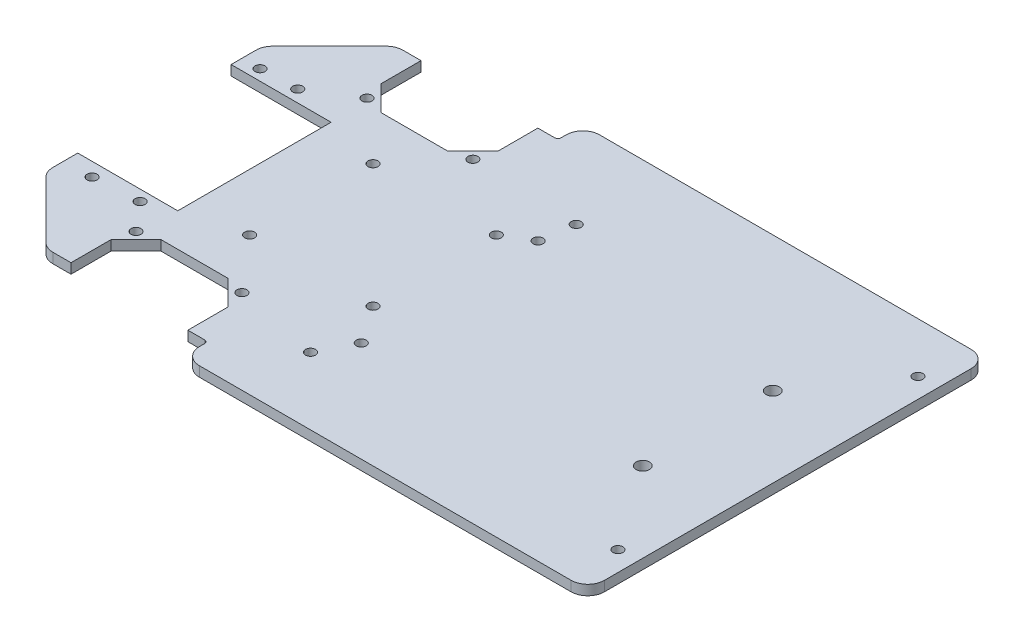
SolidWorks part; units mm, degrees
ref_plane "Front Plane" through (0, 0, 0) normal (0, 0, 1) x (1, 0, 0)
ref_plane "Top Plane" through (0, 0, 0) normal (0, 1, 0) x (1, 0, 0)
ref_plane "Right Plane" through (0, 0, 0) normal (1, 0, 0) x (0, 0, -1)
sketch "Sketch1" plane through (0, 0, 0) normal (0, 1, 0) x (1, 0, 0)
  line L0 (190, 0) -> (0, 0) construction
  line L1 (0, -60) -> (190, -60)
  line L2 (0, -60) -> (0, 60)
  line L3 (0, 60) -> (190, 60)
  line L4 (190, -60) -> (190, 60)
  line L5 (0, -32.5266) -> (27.4734, -60)
  line L6 (30, 23) -> (0, 23) construction
  line L7 (30, 23) -> (30, -23) construction
  line L8 (30, -23) -> (0, -23) construction
  line L9 (0, 23) -> (0, -23)
  line L10 (30, 23) -> (0, -23) construction
  line L11 (30, -23) -> (0, 23) construction
  line L12 (19.9734, -52.5) -> (27.4734, -52.5) construction
  line L13 (68.5266, -52.5) -> (68.5266, -60) construction
  line L14 (35, -33) -> (27.4734, -40.5266) construction
  line L15 (27.4734, -52.5) -> (27.4734, -40.5266) construction
  line L16 (27.4734, -40.5266) -> (27.4734, -52.5) construction
  line L17 (0, 32.5266) -> (27.4734, 60)
  line L18 (35, -33) -> (55, -33) construction
  line L19 (55, -33) -> (62.5266, -40.5266) construction
  line L20 (62.5266, -52.5) -> (68.5266, -52.5) construction
  line L21 (47.5, -37) -> (42.5, -37) construction
  line L22 (45, -37) -> (45, -33) construction
  line L23 (45, -56.5) -> (45, -52.5) construction
  line L24 (39.4, -56.5) -> (50.6, -56.5) construction
  line L25 (27.4734, -52.5) -> (62.5266, -52.5) construction
  line L27 (62.5266, -40.5266) -> (62.5266, -52.5) construction
  point P7 (0, 0)
  point P8 (15, 0)
  dimension "D1" = 120
  dimension "D2" = 190
  dimension "D3" = 30
  dimension "D4" = 23
  dimension "D5" = 10
  dimension "D6" = 20
  dimension "D7" = 45
  dimension "D8" = 45
  dimension "D9" = 45
  dimension "D10" = 7.5
  dimension "D11" = 6
extrude "Boss-Extrude1" add sketch "Sketch1" along normal blind 3 contours L7 L8 L2 L1 L4 L3 L6 region at (97.9391, 0, 0)
sketch "Sketch4" plane through (0, 0, 0) normal (0, 1, 0) x (1, 0, 0)
  line L0 (68.5266, -60) -> (68.5266, -52.5)
  line L1 (68.5266, -52.5) -> (62.5266, -52.5)
  line L2 (62.5266, -52.5) -> (62.5266, -40.5266)
  line L3 (62.5266, -40.5266) -> (55, -33)
  line L4 (55, -33) -> (35, -33)
  line L5 (35, -33) -> (27.4734, -40.5266)
  line L6 (27.4734, -40.5266) -> (27.4734, -52.5)
  line L7 (27.4734, -52.5) -> (19.9734, -52.5)
  line L8 (19.9734, -52.5) -> (27.4734, -60)
  line L9 (27.4734, -60) -> (68.5266, -60)
  line L10 (0, 0) -> (190, 0) construction
  line L11 (190, -60) -> (190, 60) construction
  line L12 (27.4734, 60) -> (68.5266, 60)
  line L13 (19.9734, 52.5) -> (27.4734, 60)
  line L14 (27.4734, 52.5) -> (19.9734, 52.5)
  line L15 (27.4734, 40.5266) -> (27.4734, 52.5)
  line L16 (35, 33) -> (27.4734, 40.5266)
  line L17 (55, 33) -> (35, 33)
  line L18 (62.5266, 40.5266) -> (55, 33)
  line L19 (62.5266, 52.5) -> (62.5266, 40.5266)
  line L20 (68.5266, 52.5) -> (62.5266, 52.5)
  line L21 (68.5266, 60) -> (68.5266, 52.5)
  line L23 (30, 23) -> (0, 23)
  line L24 (30, 23) -> (30, -23)
  line L25 (30, -23) -> (0, -23)
  line L26 (0, 23) -> (0, -23)
extrude "Cut-Extrude1" cut sketch "Sketch4" along normal up to surface (3 mm away) up to face at (72.4911, 3, 0)
fillet "Fillet1" radius 5 8 edges at (19.9734, 1.5, -52.5) (0, 1.5, -32.5266) (68.5266, 1.5, -60) (190, 1.5, -60) (190, 1.5, 60) (0, 1.5, 32.5266) (19.9734, 1.5, 52.5) (68.5266, 1.5, 60)
fillet "Fillet2" radius 1 2 edges at (68.5266, 1.5, -52.5) (68.5266, 1.5, 52.5)
sketch "Sketch5" plane through (0, 0, 0) normal (0, 1, 0) x (1, 0, 0)
  circle A0 centre (47.0626, -18.5) radius 1.5 construction
  circle A1 centre (47.0626, -18.5) radius 1.5
  circle A2 centre (84.0626, -18.5) radius 1.5 construction
  circle A3 centre (84.0626, -18.5) radius 1.5
  circle A4 centre (84.0626, 18.5) radius 1.5 construction
  circle A5 centre (84.0626, 18.5) radius 1.5
  circle A6 centre (47.0626, 18.5) radius 1.5 construction
  circle A7 centre (47.0626, 18.5) radius 1.5
  circle A8 centre (91.88, 23.2195) radius 1.5 construction
  circle A9 centre (91.88, 23.2195) radius 1.5
  circle A10 centre (93.3054, 33.2195) radius 1.5 construction
  circle A11 centre (93.3054, 33.2195) radius 1.5
  circle A12 centre (29.1154, 34.642) radius 1.5 construction
  circle A13 centre (60.8846, 34.642) radius 1.5 construction
  circle A14 centre (8.3674, -27.0854) radius 1.5 construction
  circle A15 centre (16.3794, 26.6064) radius 1.5 construction
  circle A16 centre (91.88, -29.8422) radius 1.5 construction
  circle A17 centre (86.6598, -39.8422) radius 1.5 construction
  circle A18 centre (29.1154, 34.642) radius 1.5
  circle A19 centre (60.8846, 34.642) radius 1.5
  circle A20 centre (8.3674, -27.0854) radius 1.5
  circle A21 centre (16.3794, 26.6064) radius 1.5
  circle A22 centre (91.88, -29.8422) radius 1.5
  circle A23 centre (86.6598, -39.8422) radius 1.5
  circle A24 centre (184.0458, -45) radius 1.5 construction
  circle A25 centre (184.0458, 45) radius 1.5 construction
  circle A26 centre (184.0458, -45) radius 1.5
  circle A27 centre (184.0458, 45) radius 1.5
  circle A28 centre (166, -19.5) radius 2 construction
  circle A29 centre (166, 19.5) radius 2 construction
  circle A30 centre (166, -19.5) radius 2
  circle A31 centre (166, 19.5) radius 2
  circle A32 centre (29.1154, -34.642) radius 1.5 construction
  circle A33 centre (60.8846, -34.642) radius 1.5 construction
  circle A34 centre (29.1154, -34.642) radius 1.5
  circle A35 centre (60.8846, -34.642) radius 1.5
  circle A36 centre (21.9337, -26.25) radius 1.5 construction
  circle A37 centre (5.4397, 26.25) radius 1.5 construction
  circle A38 centre (21.9337, -26.25) radius 1.5
  circle A39 centre (5.4397, 26.25) radius 1.5
extrude "Cut-Extrude2" cut sketch "Sketch5" along normal up to surface (3 mm away) up to face at (55.2686, 3, 0)
